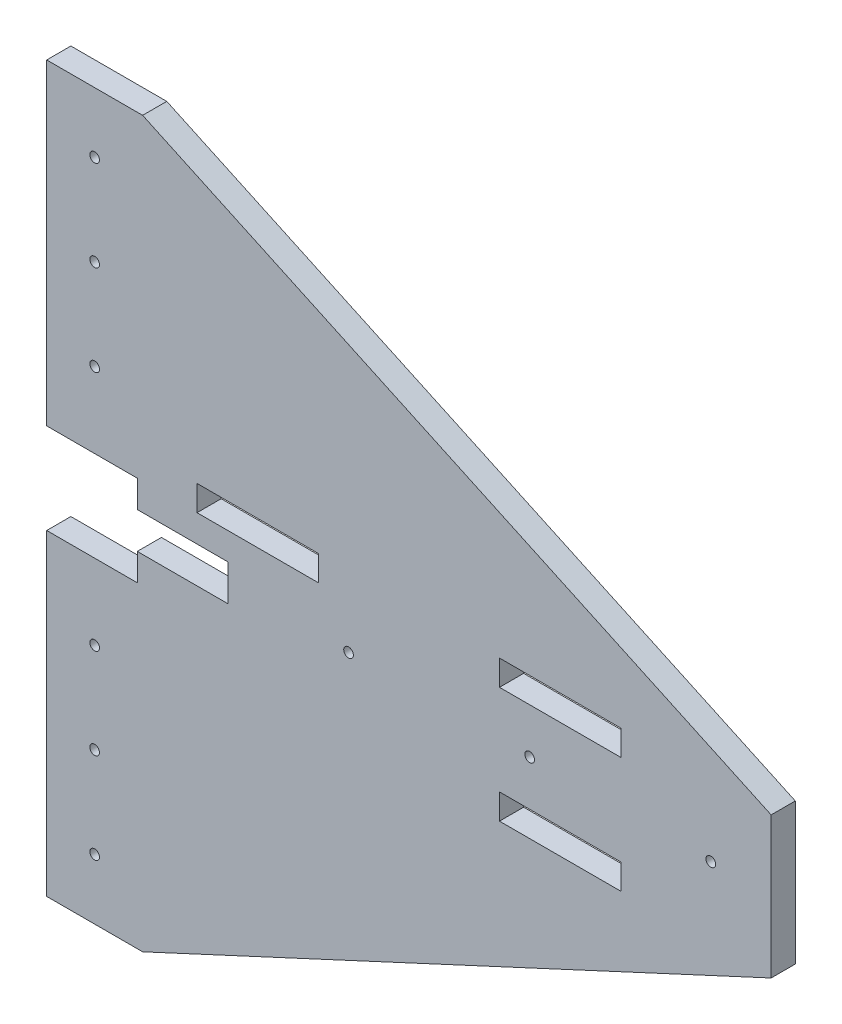
SolidWorks part; units mm, degrees
ref_plane "Front Plane" through (0, 0, 0) normal (0, 0, 1) x (1, 0, 0)
ref_plane "Top Plane" through (0, 0, 0) normal (0, 1, 0) x (1, 0, 0)
ref_plane "Right Plane" through (0, 0, 0) normal (1, 0, 0) x (0, 0, -1)
sketch "Sketch1" plane through (0, 0, 0) normal (0, 0, 1) x (1, 0, 0)
  line L0 (0, 15) -> (0, 67.5)
  line L1 (0, 0) -> (15, 0)
  line L2 (0, 67.5) -> (15.8875, 67.5)
  line L3 (0, 15) -> (15, 15)
  line L4 (15, 0) -> (15, 15)
  line L5 (15.8875, 67.5) -> (120, 19.2)
  line L6 (120, 19.2) -> (120, -4.2)
  line L7 (120, -4.2) -> (15.8875, -52.5)
  line L8 (15.8875, -52.5) -> (0, -52.5)
  line L9 (0, -52.5) -> (0, 0)
  line L10 (15, 7.5) -> (120, 7.5) construction
  line L11 (15.8875, -27.9538) -> (15.8875, -19.2091) construction
  line L15 (75, -4.2) -> (95.1, -4.2)
  line L16 (75, -4.2) -> (75, 0)
  line L17 (75, 0) -> (95.1, 0)
  line L18 (95.1, -4.2) -> (95.1, 0)
  line L19 (95.1, 19.2) -> (95.1, 15)
  line L20 (75, 15) -> (95.1, 15)
  line L21 (75, 19.2) -> (75, 15)
  line L22 (75, 19.2) -> (95.1, 19.2)
  line L23 (45, 15) -> (45, 19.2)
  line L24 (24.9, 19.2) -> (45, 19.2)
  line L25 (24.9, 15) -> (24.9, 19.2)
  line L26 (24.9, 15) -> (45, 15)
  dimension "D4" = 104.1125
  dimension "D5" = 24.9
  dimension "D1" = 15
  dimension "D2" = 30
  dimension "D3" = 60
  dimension "D8" = 23.4
  dimension "slotlength" = 20.1
  dimension "slotwidth" = 4.2
extrude "Boss-Extrude1" add sketch "Sketch1" along normal blind 4
sketch "Sketch2" plane through (0, 0, 4) normal (0, 0, 1) x (1, 0, 0)
  line L0 (7.9437, 67.5) -> (7.9437, -52.5) construction
  line L1 (15.8875, 67.5) -> (0, 67.5) construction
  line L2 (0, -52.5) -> (15.8875, -52.5) construction
  line L3 (15, 7.5) -> (120, 7.5) construction
  line L4 (15, 15) -> (15, 0) construction
  line L5 (120, -4.2) -> (120, 19.2) construction
  circle A0 centre (110, 7.5) radius 0.8
  circle A1 centre (7.9437, 57.5) radius 0.8
  dimension "D1" = 1.6
  dimension "D2" = 10
  dimension "D3" = 10
extrude "Cut-Extrude1" cut sketch "Sketch2" against normal blind 4 contours A1 region at (7.9437, 57.5, 4)
pattern_linear "LPattern2" count 3 spacing 15 along (0, -1, 0) of "Cut-Extrude1"
ref_plane "Plane1" through (0, 7.5, 0) normal (0, 1, 0) x (1, 0, 0)
mirror "Mirror1" about plane through (0, 7.5, 0) normal (0, 1, 0) of "LPattern2"
extrude "Cut-Extrude3" cut sketch "Sketch2<4>" against normal blind 4 contours A0 region at (110, 7.5, 4)
sketch "Sketch2<4>" plane through (0, 0, 4) normal (0, 0, 1) x (1, 0, 0) same geometry as "Sketch2"
pattern_linear "LPattern3" count 5 spacing 30 along (-1, 0, 0) of "Cut-Extrude3"
sketch "Sketch3" plane through (0, 0, 4) normal (0, 0, 1) x (1, 0, 0)
  line L0 (15, 15) -> (15, 0) construction
  line L1 (20, 7.5) -> (20, 10.5) construction
  line L2 (15, 4.5) -> (30, 4.5)
  line L3 (15, 4.5) -> (15, 10.5)
  line L4 (15, 10.5) -> (30, 10.5)
  line L5 (30, 4.5) -> (30, 10.5)
  line L6 (20, 7.5) -> (20, 4.5) construction
  dimension "D1" = 15
  dimension "D2" = 6
extrude "Cut-Extrude4" cut sketch "Sketch3" against normal blind 4
equation "\"obwidth\"=15"
equation "\"obchannel\"=3.2"
equation "\"bracewidth\"=120.000000"
equation "\"sheedthickness\"= 4"
equation "\"D1@Boss-Extrude1\"=\"sheedthickness\""
equation "\"D8@Sketch1\"=\"obwidth\"+2*\"slotwidth\""
equation "\"sheetthickness\"=4"
equation "\"slotwidth\"=\"sheetthickness\"+0.2"
equation "\"slotlength\"=20.1"
